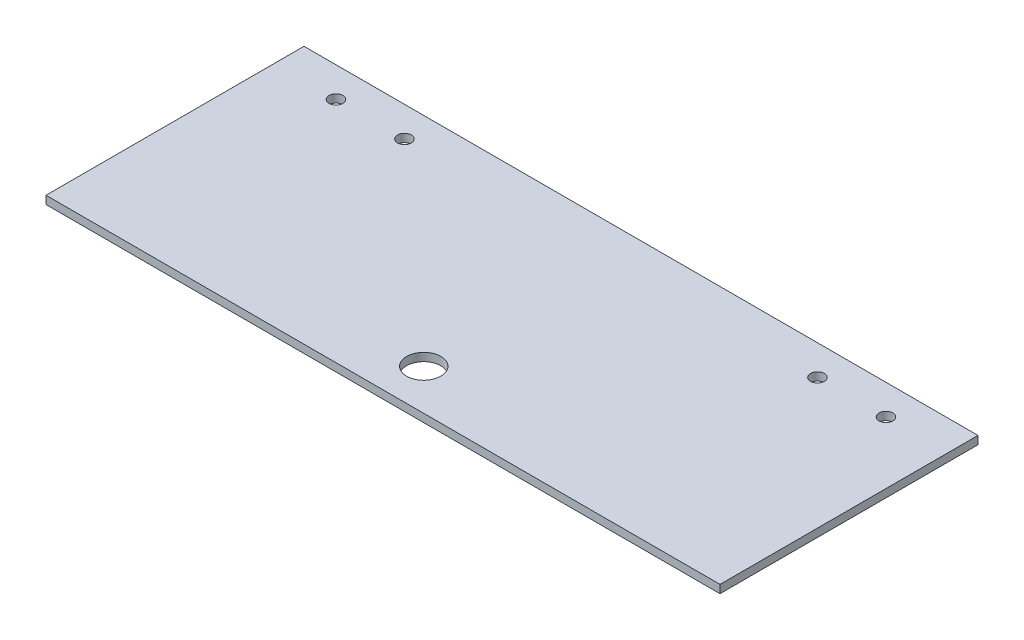
SolidWorks part; units mm, degrees
ref_plane "Front Plane" through (0, 0, 0) normal (0, 0, 1) x (1, 0, 0)
ref_plane "Top Plane" through (0, 0, 0) normal (0, 1, 0) x (1, 0, 0)
ref_plane "Right Plane" through (0, 0, 0) normal (1, 0, 0) x (0, 0, -1)
sketch "Sketch1" plane through (0, 0, 0) normal (0, 1, 0) x (1, 0, 0)
  line L0 (125, 95.7) -> (125, 0) construction
  line L1 (0, 95.7) -> (250, 95.7)
  line L2 (0, 95.7) -> (0, 0)
  line L3 (0, 0) -> (250, 0)
  line L4 (250, 95.7) -> (250, 0)
  circle A0 centre (23, 84.56) radius 2.564
  circle A1 centre (48.4, 84.56) radius 2.564
  circle A2 centre (201.6, 84.56) radius 2.564
  circle A3 centre (227, 84.56) radius 2.564
  circle A4 centre (125, 15.1) radius 6.35
  dimension "D2" = 5.128
  dimension "D7" = 12.7
  dimension "D8" = 15.1
  dimension "D1" = 250
  dimension "D3" = 25.4
  dimension "D4" = 23
  dimension "D5" = 11.14
  dimension "D6" = 84.56
extrude "Boss-Extrude1" add sketch "Sketch1" along normal blind 3
equation "\"cf_tube_outer_diameter\"= 25mm"
equation "\"cf_tube_inner_diameter\" = 21mm"
equation "\"mid_plate_mid_to_top\" = 100mm"
equation "\"mid_plate_mid_to_bottom\" = 30mm"
equation "\"mid_plate_horizontal_spacing\"=250mm"
equation "\"cf_plate_thickness\" =4mm"
equation "\"mid_tube_length\" = 121mm"
equation "\"mid_plate_bottom_width\" = 180mm"
equation "\"mid_support_plate_distance\" = 250mm"
equation "\"nut_strip_2_hole_distance\" = 7mm"
equation "\"nut_strip_hole_diameter\" = 2.5mm"
equation "\"nut_strip_hole_to_edge_distance\"= 2.5mm"
